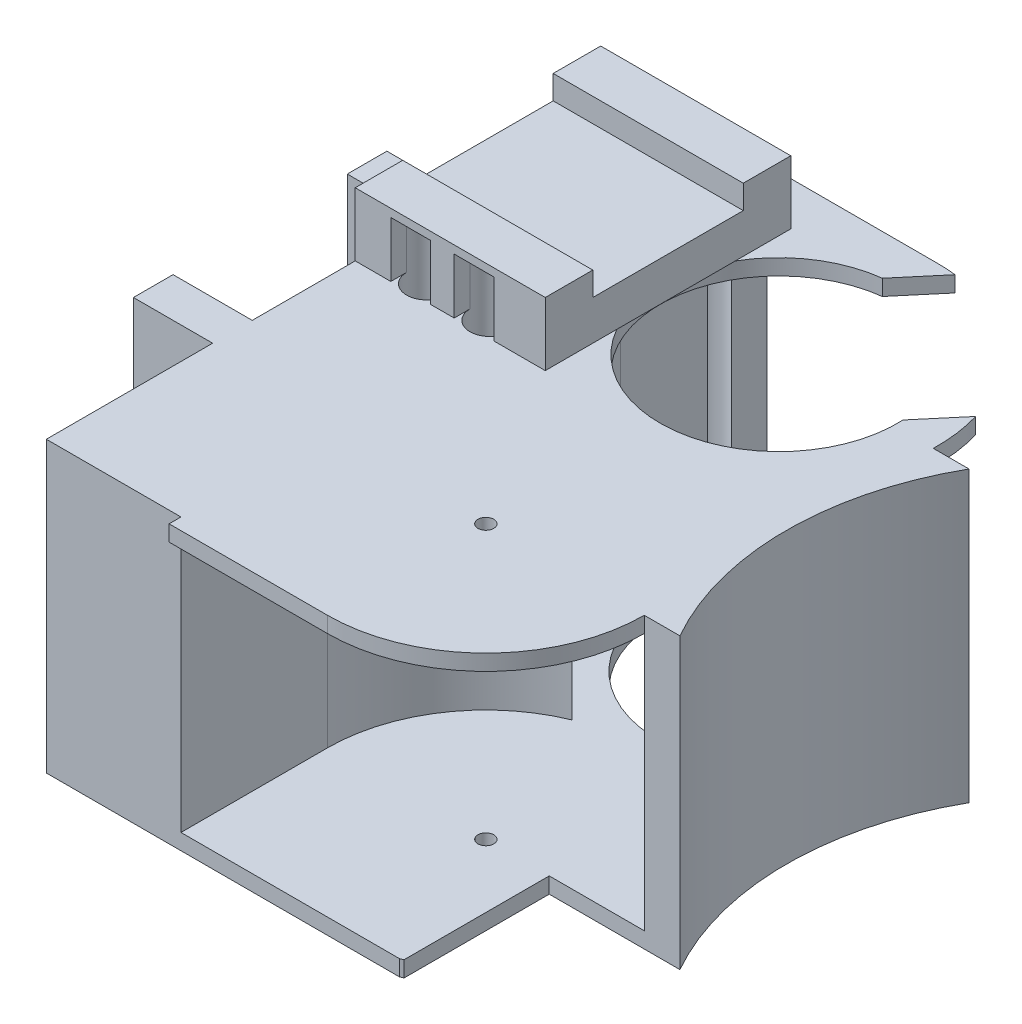
SolidWorks part; units mm, degrees
ref_plane "Front" through (0, 0, 0) normal (0, 0, 1) x (1, 0, 0)
ref_plane "Top" through (0, 0, 0) normal (0, 1, 0) x (1, 0, 0)
ref_plane "Right" through (0, 0, 0) normal (1, 0, 0) x (0, 0, -1)
sketch "Sketch1" plane through (0, 0, 0) normal (0, 1, 0) x (1, 0, 0)
  line L0 (45, 0) -> (45, 18.5)
  line L1 (0, 0) -> (45, 0)
  line L2 (0, 0) -> (0, 21)
  line L3 (0, 74) -> (22, 74)
  line L4 (0, 26) -> (-10, 26)
  line L5 (45, 18.5) -> (61.5, 18.5)
  line L6 (-10, 26) -> (-10, 21)
  line L7 (51.9917, 55) -> (61.5, 55)
  line L8 (22, 55.5) -> (22, 74)
  line L9 (-10, 21) -> (0, 21)
  line L10 (0, 48) -> (-10, 48)
  line L11 (-10, 48) -> (-10, 53)
  line L12 (-10, 53) -> (0, 53)
  line L13 (0, 53) -> (0, 74)
  line L14 (0, 26) -> (0, 48)
  line L15 (17, 18.5) -> (17, 0)
  line L16 (17, 55.5) -> (17, 74)
  circle A1 centre (7, 68) radius 2
  circle A2 centre (15, 68) radius 2.5
  circle A3 centre (7, 40) radius 2
  circle A4 centre (15, 40) radius 2
  arc A5 (57, 18.5) -> (44.5993, 37) centre (37, 18.5) ccw
  arc A6 (22, 55.5) -> (51.9917, 55) centre (37, 55.5) ccw
  arc A7 (61.5, 55) -> (61.5, 18.5) centre (93.686, 36.75) ccw
  circle A8 centre (37, 18.5) radius 1
  arc A9 (17, 55.5) -> (29.4007, 37) centre (37, 55.5) ccw
  arc A10 (44.5993, 0) -> (45, 0.1697) centre (37, 18.5) ccw
  arc A11 (44.5993, 37) -> (56.9937, 55) centre (37, 55.5) ccw
  arc A12 (29.4007, 37) -> (17, 18.5) centre (37, 18.5) ccw
extrude "Boss-Extrude18" add sketch "Sketch1" along normal blind 34.5 contours A12 A9 L16 A2 L3 L13 L12 L11 L10 L14 L4 L6 L9 L2 L1 L15 A4 A3 A1 | A11 A5 L5 A7 L7 | A9 A12 L15 L1 A10 L0 L5 A5 A11 L7 A6 L8 L3 L16 A2 A8 region at (33.7823, 0, -26.0854) region at (8.4973, 0, -36.2707) region at (54.8883, 0, -36.934)
sketch "Sketch7" plane through (0, 34.5, 0) normal (0, 1, 0) x (1, 0, 0)
  line L0 (17, 55.5) -> (17, 75.5)
  line L1 (17, 75.5) -> (37, 75.5)
  line L2 (17, 18.5) -> (17, -1.5)
  line L3 (17, -1.5) -> (37, -1.5)
  arc A0 (37, -1.5) -> (44.5993, 37) centre (37, 18.5) ccw
  arc A1 (17, 55.5) -> (29.4007, 37) centre (37, 55.5) ccw
  arc A2 (29.4007, 37) -> (17, 18.5) centre (37, 18.5) ccw
  arc A3 (44.5993, 37) -> (37, 75.5) centre (37, 55.5) ccw
extrude "Cut-Extrude16" cut sketch "Sketch7" against normal blind 32.5
sketch "Sketch8" plane through (0, 34.5, 0) normal (0, 1, 0) x (1, 0, 0)
  line L0 (17, 18.5) -> (17, -1.5)
  line L1 (17, -1.5) -> (37, -1.5)
  line L2 (17, 55.5) -> (17, 75.5)
  line L3 (17, 75.5) -> (37, 75.5)
  arc A0 (29.4007, 37) -> (17, 18.5) centre (37, 18.5) ccw
  arc A1 (44.5993, 37) -> (37, 75.5) centre (37, 55.5) ccw
  arc A2 (37, -1.5) -> (44.5993, 37) centre (37, 18.5) ccw
  arc A3 (17, 55.5) -> (29.4007, 37) centre (37, 55.5) ccw
extrude "Boss-Extrude21" add sketch "Sketch8" against normal blind 2
sketch "Sketch9" plane through (0, 34.5, 0) normal (0, 1, 0) x (1, 0, 0)
  line L0 (24, 68) -> (0, 68)
  line L1 (24, 68) -> (24, 40)
  line L2 (24, 40) -> (0, 40)
  line L3 (0, 26) -> (0, 48) construction
  circle A0 centre (7, 40) radius 2
  circle A1 centre (15, 40) radius 2
extrude "Boss-Extrude22" add sketch "Sketch9" against normal blind 34.5 contours A0
sketch "Sketch10" plane through (0, 34.5, 0) normal (0, 1, 0) x (1, 0, 0)
  circle A0 centre (15, 40) radius 2
extrude "Boss-Extrude23" add sketch "Sketch10" against normal blind 34.5
sketch "Sketch11" plane through (0, 34.5, 0) normal (0, 1, 0) x (1, 0, 0)
  circle A0 centre (7, 41) radius 2
  circle A1 centre (15, 41) radius 2
extrude "Cut-Extrude17" cut sketch "Sketch11" against normal blind 34.5
sketch "Sketch12" plane through (0, 34.5, 0) normal (0, 1, 0) x (1, 0, 0)
  line L0 (0, 68) -> (24, 68)
  line L1 (24, 68) -> (24, 41)
  line L2 (24, 41) -> (0, 41)
  line L3 (0, 26) -> (0, 48) construction
  line L4 (0, 41) -> (0, 68)
extrude "Boss-Extrude24" add sketch "Sketch12" along normal blind 8
sketch "Sketch13" plane through (0, 42.5, 0) normal (0, 1, 0) x (1, 0, 0)
  line L0 (24, 45) -> (0, 45)
  line L1 (24, 41) -> (24, 68) construction
  line L2 (0, 68) -> (0, 41) construction
  line L3 (24, 64) -> (0, 64)
  line L4 (0, 45) -> (0, 64)
  line L5 (24, 45) -> (24, 64)
sketch "Sketch15" plane through (0, 42.5, 0) normal (0, 1, 0) x (1, 0, 0)
extrude "Cut-Extrude18" cut sketch "Sketch13" against normal blind 3
sketch "Sketch16" plane through (0, 0, 0) normal (0, -1, 0) x (-1, 0, 0)
  circle A1 centre (-7, 68) radius 2.5
extrude "Cut-Extrude21" cut sketch "Sketch16" against normal blind 41.5
sketch "Sketch20" plane through (0, 0, 0) normal (0, -1, 0) x (-1, 0, 0)
  circle A0 centre (-15, 68) radius 2.5
extrude "Cut-Extrude22" cut sketch "Sketch20" against normal blind 41.5
sketch "Sketch21" plane through (0, 0, 0) normal (0, -1, 0) x (-1, 0, 0)
  circle A0 centre (-7, 41) radius 2.5
extrude "Cut-Extrude23" cut sketch "Sketch21" against normal blind 41.5
sketch "Sketch22" plane through (0, 0, 0) normal (0, -1, 0) x (-1, 0, 0)
  circle A0 centre (-15, 41) radius 2.5
extrude "Cut-Extrude24" cut sketch "Sketch22" against normal blind 41.5
sketch "Sketch23" plane through (0, 0, -68) normal (0, 0, -1) x (-1, 0, 0)
  line L0 (-24, 39.5952) -> (-24, 42.5)
  line L1 (-24, 42.5) -> (-24, 34.5) construction
  line L14 (-17.5, 41.5) -> (-12.5, 41.5)
  line L15 (-12.5, 41.5) -> (-12.5, 34.5)
  line L16 (-12.5, 34.5) -> (-9.5, 34.5)
  line L17 (-9.5, 34.5) -> (-9.5, 41.5)
  line L18 (-9.5, 41.5) -> (-4.5, 41.5)
  line L19 (-4.5, 41.5) -> (-4.5, 34.5)
  line L20 (-4.5, 34.5) -> (0, 34.5)
  line L21 (0, 34.5) -> (0, 42.5)
  line L22 (0, 42.5) -> (-24, 42.5)
  line L23 (-24, 42.5) -> (-24, 34.5)
  line L24 (-24, 34.5) -> (-17.5, 34.5)
  line L25 (-17.5, 34.5) -> (-17.5, 41.5)
  line L26 (-17.5, 41.5) -> (-12.5, 41.5)
  line L27 (-12.5, 41.5) -> (-12.5, 34.5)
  line L28 (-12.5, 34.5) -> (-9.5, 34.5)
  line L29 (-9.5, 34.5) -> (-9.5, 41.5)
  line L30 (-9.5, 41.5) -> (-4.5, 41.5)
  line L31 (-4.5, 41.5) -> (-4.5, 34.5)
  line L32 (-4.5, 34.5) -> (0, 34.5)
  line L33 (0, 34.5) -> (0, 42.5)
  line L34 (0, 42.5) -> (-24, 42.5)
  line L35 (-24, 39.5952) -> (-24, 34.5)
  line L36 (-24, 34.5) -> (-17.5, 34.5)
  line L37 (-17.5, 34.5) -> (-17.5, 41.5)
  dimension "D1" = 0
extrude "Boss-Extrude25" add sketch "Sketch23" along normal blind 2
sketch "Sketch25" plane through (0, 0, -41) normal (0, 0, 1) x (1, 0, 0)
sketch "Sketch26" plane through (0, 0, -41) normal (0, 0, 1) x (1, 0, 0)
  line L0 (19.8714, 42.5) -> (24, 42.5)
  line L1 (0, 42.5) -> (24, 42.5) construction
  line L2 (24, 42.5) -> (24, 34.5)
  line L3 (24, 34.5) -> (17.5, 34.5)
  line L4 (17.5, 34.5) -> (17.5, 41.5)
  line L5 (17.5, 41.5) -> (12.5, 41.5)
  line L6 (12.5, 41.5) -> (12.5, 34.5)
  line L7 (12.5, 34.5) -> (9.5, 34.5)
  line L8 (9.5, 34.5) -> (9.5, 41.5)
  line L9 (9.5, 41.5) -> (4.5, 41.5)
  line L10 (4.5, 41.5) -> (4.5, 34.5)
  line L11 (4.5, 34.5) -> (0, 34.5)
  line L12 (0, 34.5) -> (0, 42.5)
  line L13 (0, 42.5) -> (19.8714, 42.5)
extrude "Boss-Extrude26" add sketch "Sketch26" along normal blind 2
sketch "Sketch27" plane through (0, 0, -53) normal (0, 0, -1) x (-1, 0, 0)
  circle A0 centre (5, 8.75) radius 1
  circle A1 centre (5, 25.75) radius 1
extrude "Cut-Extrude27" cut sketch "Sketch27" against normal blind 5
sketch "Sketch28" plane through (0, 0, -26) normal (0, 0, -1) x (-1, 0, 0)
  circle A0 centre (5, 8.75) radius 1
  circle A1 centre (5, 25.75) radius 1
extrude "Cut-Extrude28" cut sketch "Sketch28" against normal blind 5
sketch "Sketch29" plane through (0, 32.5, 0) normal (0, -1, 0) x (1, 0, 0)
  circle A0 centre (37, -55.5) radius 15
extrude "Cut-Extrude29" cut sketch "Sketch29" against normal blind 2
sketch "Sketch30" plane through (0, 32.5, 0) normal (0, -1, 0) x (-1, 0, 0)
  circle A0 centre (-37, 18.5) radius 1
extrude "Cut-Extrude30" cut sketch "Sketch30" against normal blind 2
sketch "Sketch31" plane through (0, 34.5, 0) normal (0, 1, 0) x (1, 0, 0)
  line L0 (45.4038, 48.4023) -> (28.5962, 62.5977)
  line L1 (28.5962, 62.5977) -> (39.3739, 75.3586)
  line L2 (45.4038, 48.4023) -> (56.1814, 61.1633)
  arc A1 (56.9937, 55) -> (37, 75.5) centre (37, 55.5) ccw construction
extrude "Cut-Extrude31" cut sketch "Sketch31" against normal blind 10 and the other way through all
sketch "Sketch32" plane through (0, 0, 0) normal (0, -1, 0) x (-1, 0, 0)
  line L0 (0, 74) -> (0, 53)
  line L1 (0, 53) -> (10, 53)
  line L2 (10, 53) -> (10, 48)
  line L3 (10, 48) -> (0, 48)
  line L4 (0, 48) -> (0, 26)
  line L5 (0, 26) -> (10, 26)
  line L6 (10, 26) -> (10, 21)
  line L7 (10, 21) -> (0, 21)
  line L8 (0, 21) -> (0, 0)
  line L9 (0, 0) -> (-44.5993, 0)
  line L10 (-45, 0.1697) -> (-45, 18.5)
  line L11 (-45, 18.5) -> (-61.5, 18.5)
  line L12 (0, 0) -> (-44.5993, 0) construction
  line L13 (-44.5993, 0) -> (-45, 0.1697)
  line L14 (-61.5, 18.5) -> (-61.5, 55)
  line L15 (-22, 55.5) -> (-51.9917, 55)
  line L17 (-61.5, 55) -> (-51.9917, 55)
  line L28 (-22, 55.5) -> (-22, 74)
  line L29 (-22, 74) -> (0, 74)
  circle A0 centre (-7, 68) radius 2.5
  circle A1 centre (-7, 41) radius 2.5
  circle A2 centre (-15, 68) radius 2.5
  circle A3 centre (-15, 41) radius 2.5
  circle A4 centre (-37, 18.5) radius 1
extrude "Boss-Extrude28" add sketch "Sketch32" along normal blind 2
sketch "Sketch34" plane through (0, -2, 0) normal (0, -1, 0) x (-1, 0, 0)
  line L0 (-61.5, 18.5) -> (-45, 18.5) construction
  line L1 (-61.5, 55) -> (-61.5, 18.5) construction
  line L2 (-61.5, 55) -> (-61.5, 18.5)
  arc A0 (-61.5, 55) -> (-61.5, 18.5) centre (-93.686, 36.75) cw
extrude "Cut-Extrude32" cut sketch "Sketch34" against normal blind 2
sketch "Sketch35" plane through (0, -2, 0) normal (0, -1, 0) x (-1, 0, 0)
  line L0 (-22, 55.5) -> (-51.9917, 55) construction
  circle A0 centre (-36.9968, 55.25) radius 15
extrude "Cut-Extrude33" cut sketch "Sketch35" against normal blind 2
sketch "Sketch36" plane through (0, -2, 0) normal (0, -1, 0) x (-1, 0, 0)
  line L0 (-17, 55.5) -> (-17, 74)
  line L1 (0, 74) -> (-22, 74) construction
  line L3 (-17, 74) -> (-37, 75.5)
  arc A0 (-34.0168, 75.2763) -> (-17, 55.5) centre (-37, 55.5) ccw
  circle A1 centre (-15, 68) radius 2.5
extrude "Boss-Extrude30" add sketch "Sketch36" against normal blind 2 from offset 2 contours A1 offset against normal yes
sketch "Sketch38" plane through (0, -2, 0) normal (0, -1, 0) x (1, 0, 0)
  line L0 (17, -75.5) -> (57, -75.5)
  line L1 (17, -55.5) -> (17, -75.5)
  line L2 (57, -75.5) -> (57, -55.5)
  arc A1 (57, -55.5) -> (17, -55.5) centre (37, -55.5) ccw
extrude "Cut-Extrude40" cut sketch "Sketch38" against normal blind 2 from offset 2 offset against normal yes
sketch "Sketch39" plane through (0, 0, 0) normal (0, -1, 0) x (-1, 0, 0)
  circle A0 centre (-15, 68) radius 2.5
extrude "Cut-Extrude41" cut sketch "Sketch39" against normal blind 2
sketch "Sketch41" plane through (0, -2, 0) normal (0, -1, 0) x (-1, 0, 0)
  line L0 (-17, 18.5) -> (-17, -1.5)
  line L1 (-17, -1.5) -> (-37, -1.5)
  line L2 (-37, -1.5) -> (-57, -1.5)
  line L3 (-57, -1.5) -> (-57, 18.5)
  arc A0 (-17, 18.5) -> (-57, 18.5) centre (-37, 18.5) ccw
extrude "Cut-Extrude42" cut sketch "Sketch41" against normal blind 2 from offset 2 offset against normal yes
sketch "Sketch42" plane through (0, 0, -26) normal (0, 0, -1) x (-1, 0, 0)
  circle A0 centre (5, 8.75) radius 1
extrude "Boss-Extrude31" add sketch "Sketch42" against normal blind 5
sketch "Sketch43" plane through (0, 0, -26) normal (0, 0, -1) x (-1, 0, 0)
  circle A0 centre (5, 8.25) radius 1
extrude "Cut-Extrude44" cut sketch "Sketch43" against normal blind 5
sketch "Sketch46" plane through (0, 0, -26) normal (0, 0, -1) x (-1, 0, 0)
  circle A0 centre (5, 25.75) radius 1
extrude "Boss-Extrude32" add sketch "Sketch46" against normal blind 5
sketch "Sketch47" plane through (0, 0, -26) normal (0, 0, -1) x (-1, 0, 0)
  circle A0 centre (5, 24.25) radius 1
extrude "Cut-Extrude45" cut sketch "Sketch47" against normal blind 5
sketch "Sketch48" plane through (0, 0, -53) normal (0, 0, -1) x (-1, 0, 0)
  circle A0 centre (5, 8.75) radius 1
extrude "Boss-Extrude33" add sketch "Sketch48" against normal blind 5
sketch "Sketch49" plane through (0, 0, -53) normal (0, 0, -1) x (-1, 0, 0)
  circle A0 centre (5, 8.25) radius 1
extrude "Cut-Extrude46" cut sketch "Sketch49" against normal blind 5
sketch "Sketch50" plane through (0, 0, -53) normal (0, 0, -1) x (-1, 0, 0)
  circle A0 centre (5, 25.75) radius 1
extrude "Boss-Extrude34" add sketch "Sketch50" against normal blind 5
sketch "Sketch51" plane through (0, 0, -53) normal (0, 0, -1) x (-1, 0, 0)
  circle A0 centre (5, 24.25) radius 1
extrude "Cut-Extrude47" cut sketch "Sketch51" against normal blind 5
ref_plane "Plane1" through (61.5, 0, 0) normal (1, 0, 0) x (0, 0, -1)
